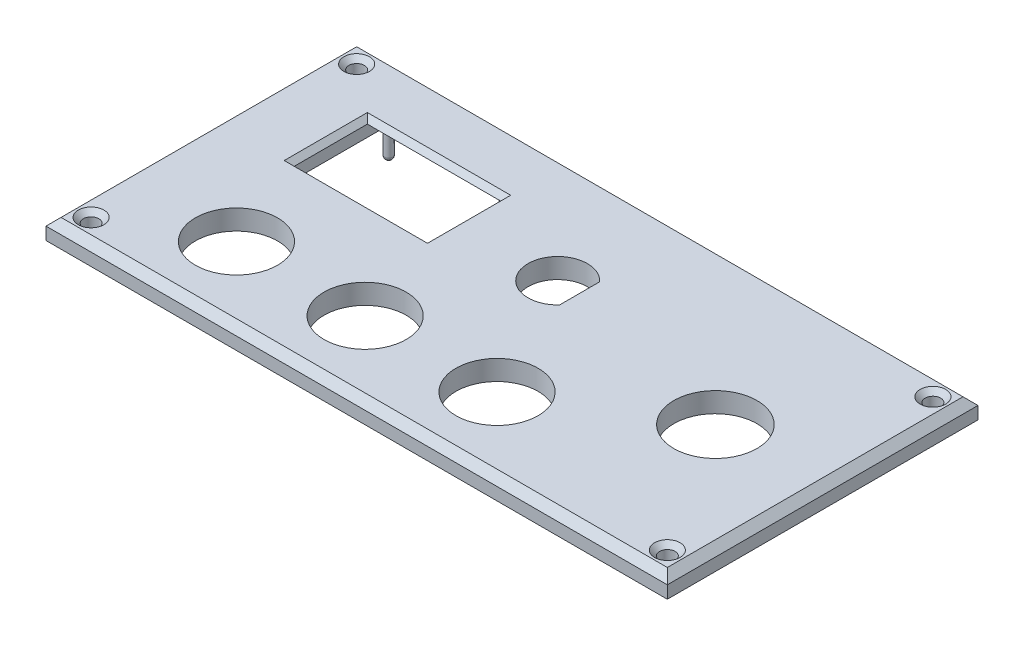
SolidWorks part; units mm, degrees
ref_plane "Front Plane" through (0, 0, 0) normal (0, 0, 1) x (1, 0, 0)
ref_plane "Top Plane" through (0, 0, 0) normal (0, 1, 0) x (1, 0, 0)
ref_plane "Right Plane" through (0, 0, 0) normal (1, 0, 0) x (0, 0, -1)
sketch "Sketch2" plane through (0, 0, 0) normal (0, 1, 0) x (1, 0, 0)
  line L0 (-55.3925, 57.5) -> (145.2566, 57.5) construction
  line L1 (0, 0) -> (124, 0)
  line L2 (0, 0) -> (0, 62)
  line L3 (0, 62) -> (124, 62)
  line L4 (124, 0) -> (124, 62)
  line L5 (4.5, 83.9208) -> (4.5, -17.3547) construction
  line L6 (-55.3925, 4.5) -> (145.2566, 4.5) construction
  line L7 (119.5, 83.9208) -> (119.5, -17.3547) construction
  line L8 (3.6, 51.9) -> (3.6, 10.1)
  line L9 (-12.602, 31) -> (135.6682, 31) construction
  line L10 (135.6682, 31) -> (20.7736, 31) construction
  line L11 (10.1, 58.4) -> (113.9, 58.4)
  line L12 (3.6, 51.9) -> (10.1, 51.9)
  line L13 (3.6, 51.9) -> (3.6, 10.1)
  line L14 (3.6, 10.1) -> (10.1, 10.1)
  line L15 (120.4, 51.9) -> (120.4, 10.1)
  line L16 (62, 70.8482) -> (62, -22.3665) construction
  line L17 (113.9, 51.9) -> (120.4, 51.9)
  line L18 (10.1, 58.4) -> (113.9, 58.4)
  line L19 (10.1, 58.4) -> (10.1, 51.9)
  line L20 (10.1, 3.6) -> (113.9, 3.6)
  line L21 (113.9, 58.4) -> (113.9, 51.9)
  line L22 (10.1, 10.1) -> (10.1, 3.6)
  line L23 (113.9, 10.1) -> (120.4, 10.1)
  line L24 (113.9, 10.1) -> (113.9, 3.6)
  line L25 (66.375, 44.1149) -> (66.375, 36.1237)
  line L26 (14.9397, 49.1974) -> (41.5397, 49.1974)
  line L27 (14.9397, 49.1974) -> (14.9397, 34.5974)
  line L28 (14.9397, 34.5974) -> (41.5397, 34.5974)
  line L29 (41.5397, 49.1974) -> (41.5397, 34.5974)
  line L31 (14.2397, 53.7974) -> (42.2397, 53.7974)
  line L32 (14.2397, 53.7974) -> (14.2397, 25.4474)
  line L33 (14.2397, 25.4474) -> (42.2397, 25.4474)
  line L34 (42.2397, 53.7974) -> (42.2397, 25.4474)
  circle A0 centre (4.5, 57.5) radius 1.55
  circle A1 centre (119.5, 4.5) radius 1.55
  circle A2 centre (119.5, 57.5) radius 1.55
  circle A3 centre (4.5, 4.5) radius 1.55
  circle A4 centre (102.5933, 31) radius 8.3
  circle A5 centre (102.5933, 31) radius 12.375
  circle A6 centre (75.1711, 14.8396) radius 8.2
  circle A7 centre (75.1711, 14.8396) radius 8.95
  circle A8 centre (39.7997, 51.7093) radius 0.8
  circle A9 centre (39.7997, 28.4093) radius 0.8
  circle A10 centre (16.6797, 28.4093) radius 0.8
  circle A11 centre (16.6797, 51.7093) radius 0.8
  circle A12 centre (62, 40.1193) radius 5.925
  circle A13 centre (62, 40.1193) radius 7.25
  circle A14 centre (48.8465, 14.8396) radius 8.2
  circle A15 centre (48.8465, 14.8396) radius 8.95
  circle A16 centre (23.1711, 14.8396) radius 8.2
  circle A17 centre (23.1711, 14.8396) radius 8.95
  point P25 (0, 31)
  point P27 (3.6, 31)
  point P34 (62, 62)
  point P35 (62, 58.4)
  point P60 (0, 0)
  point P61 (28.2397, 34.5974)
  point P77 (28.2397, 53.7974)
  point P78 (28.2397, 49.1974)
  point P79 (0, 0)
  point P80 (0, 0)
  point P81 (0, 0)
  point P82 (0, 0)
  dimension "D7" = 3.1
  dimension "D14" = 16.6
  dimension "D15" = 24.75
  dimension "D16" = 16.4
  dimension "D17" = 17.9
  dimension "D20" = 1.6
  dimension "D21" = 23.3
  dimension "D25" = 11.85
  dimension "D26" = 14.5
  dimension "D28" = 28.35
  dimension "D1" = 62
  dimension "D2" = 124
  dimension "D3" = 4.5
  dimension "D4" = 4.5
  dimension "D5" = 4.5
  dimension "D6" = 4.5
  dimension "D8" = 41.8
  dimension "D9" = 3.6
  dimension "D10" = 3.6
  dimension "D11" = 103.8
  dimension "D12" = 3.6
  dimension "D13" = 3.6
  dimension "D18" = 14.6
  dimension "D19" = 26.6
  dimension "D23" = 11.56
  dimension "D24" = 11.56
  dimension "D27" = 4.375
  dimension "D29" = 28
  dimension "D30" = 4.6
extrude "Boss-Extrude1" add sketch "Sketch2" along normal blind 4 contours L24 L23 L15 L17 L21 L11 L19 L12 L8 L14 L22 L20 A17 A15 A13 A11 A10 A9 A8 A7 A5 L26 L29 L28 L27 | L1 L4 L3 L2 A3 A2 A1 A0 L23 L24 L20 L22 L14 L8 L12 L19 L11 L21 L17 L15 | A10 | A9 | A8 | A11 | L34 L31 L32 L33 A11 A10 A9 A8 L26 L29 L28 L27 | A13 A12 | A5 A4 | A7 A6 | A15 A14 | A17 A16 | L25 A12 region at (1.3864, 0, -31) region at (66.2203, 0, -31.9537) region at (67.0025, 0, -40.1193) region at (28.2397, 0, -53.3989) region at (90.5683, 0, -31) region at (66.4742, 0, -14.8396) region at (39.7997, 0, -51.7093) region at (39.7997, 0, -28.4093) region at (16.6797, 0, -28.4093) region at (16.6797, 0, -51.7093) region at (54.9551, 0, -40.1193) region at (40.1497, 0, -14.8396) region at (14.4742, 0, -14.8396)
chamfer "Chamfer1" distance 1.5 angle 45 4 edges at (124, 4, -31) (62, 4, -62) (62, 4, 0) (0, 4, -31)
chamfer "Chamfer2" distance 1 angle 45 5 edges at (119.5, 0, -55.95) (119.5, 4, -55.95) (4.5, 4, -2.95) (119.5, 4, -2.95) (4.5, 4, -55.95)
extrude "Boss-Extrude2" add sketch "Sketch2<3>" against normal blind 3.5 contours A10 | A11 | A9 | A8 region at (16.6797, 0, -28.4093) region at (16.6797, 0, -51.7093)
sketch "Sketch2<3>" plane through (0, 0, 0) normal (0, 1, 0) x (1, 0, 0) same geometry as "Sketch2"
fillet "Fillet1" radius 0.8 4 edges at (39.7997, -3.5, -27.6093) (16.6797, -3.5, -27.6093) (16.6797, -3.5, -50.9093) (39.7997, -3.5, -50.9093)
extrude "Cut-Extrude1" cut sketch "Sketch2<4>" along normal blind 3 contours L34 L31 L32 L33 A11 A10 A9 A8 L26 L29 L28 L27 region at (28.2397, 0, -53.3989)
sketch "Sketch2<4>" plane through (0, 0, 0) normal (0, 1, 0) x (1, 0, 0) same geometry as "Sketch2"
chamfer "Chamfer3" distance 1 angle 45 4 edges at (28.2397, 4, -34.5974) (41.5397, 4, -41.8974) (14.9397, 4, -41.8974) (28.2397, 4, -49.1974)
